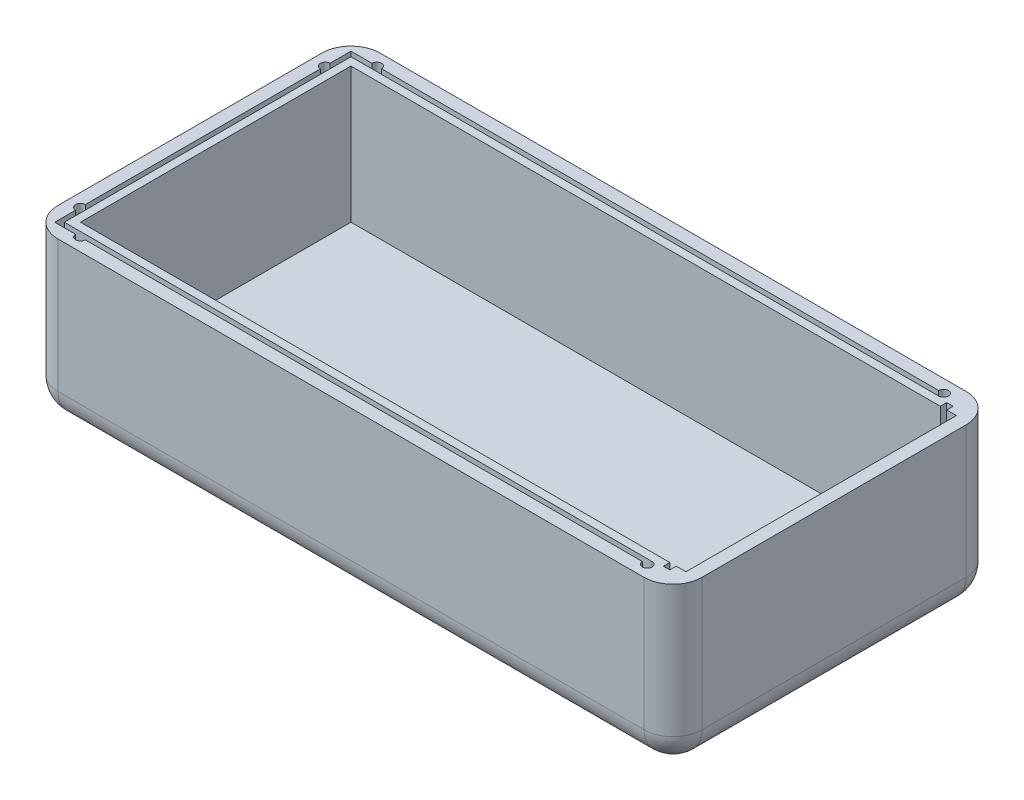
SolidWorks part; units mm, degrees
other "Исправление1"
sketch "Эскиз3"
other "Исправление2"
sketch "Эскиз4"
other "Исправление3"
sketch "Эскиз5" plane through (0, 25, 70) normal (-0.7989, 0.4591, 0.3886) x (0.5563, 0.3183, 0.7676)
other "Детальный элемент1"
other "Детальный элемент2"
other "Детальный элемент3"
ref_plane "Спереди" through (0, 0, 0) normal (0, 0, 1) x (1, 0, 0)
ref_plane "Сверху" through (0, 0, 0) normal (0, 1, 0) x (1, 0, 0)
ref_plane "Справа" through (0, 0, 0) normal (1, 0, 0) x (0, 0, -1)
sketch "Эскиз1" plane through (0, 0, 0) normal (0, 1, 0) x (1, 0, 0)
  line L1 (0, 0) -> (100, 0)
  line L2 (0, 0) -> (0, -50)
  line L3 (0, -50) -> (100, -50)
  line L4 (100, 0) -> (100, -50)
  dimension "D1" = 50
  dimension "D2" = 100
extrude "Бобышка-Вытянуть1" add sketch "Эскиз1" along normal blind 25
shell "Оболочка1" thickness 4 removed face at (50, 25, 25)
fillet "Скругление1" radius 4.5 8 edges at (50, 0, 50) (100, 0, 25) (50, 0, 0) (0, 0, 25) (100, 12.5, 0) (100, 12.5, 50) (0, 12.5, 0) (0, 12.5, 50)
sketch "Эскиз2" plane through (0, 25, 0) normal (0, 1, 0) x (1, 0, 0)
  line L0 (50, -4) -> (50, -46) construction
  line L1 (96, -4) -> (4, -4) construction
  line L2 (4, -46) -> (96, -46) construction
  line L3 (4, -25) -> (96, -25) construction
  line L4 (4, -4) -> (4, -46) construction
  line L5 (96, -46) -> (96, -4) construction
  line L6 (95.5, 0) -> (4.5, 0) construction
  line L7 (4, -4) -> (4, -46) construction
  line L8 (96, -4) -> (4, -4) construction
  line L9 (2.75, -6) -> (2.75, -2.75)
  line L10 (6, -2.75) -> (2.75, -2.75)
  line L11 (2, -5.25) -> (2, -2)
  line L12 (2, -2) -> (5.25, -2)
  line L13 (97.25, -6) -> (97.25, -2.75)
  line L14 (98, -5.25) -> (98, -2)
  line L15 (94, -2.75) -> (97.25, -2.75)
  line L16 (98, -2) -> (94.75, -2)
  line L17 (98, -48) -> (94.75, -48)
  line L18 (94, -47.25) -> (97.25, -47.25)
  line L19 (98, -44.75) -> (98, -48)
  line L20 (97.25, -44) -> (97.25, -47.25)
  line L21 (2, -48) -> (5.25, -48)
  line L22 (2, -44.75) -> (2, -48)
  line L23 (6, -47.25) -> (2.75, -47.25)
  line L24 (2.75, -44) -> (2.75, -47.25)
  line L25 (2, -6.75) -> (2, -43.25)
  line L26 (2.75, -44) -> (2.75, -6)
  line L27 (6, -2.75) -> (94, -2.75)
  line L28 (93.25, -2) -> (6.75, -2)
  line L29 (98, -6.75) -> (98, -43.25)
  line L30 (97.25, -6) -> (97.25, -44)
  line L31 (94, -47.25) -> (6, -47.25)
  line L32 (6.75, -48) -> (93.25, -48)
  line L33 (97.25, -47.25) -> (97.25, -48)
  line L34 (97.25, -2.75) -> (97.25, -2)
  circle A0 centre (6, -2) radius 0.75
  circle A1 centre (2, -6) radius 0.75
  circle A2 centre (98, -6) radius 0.75
  circle A3 centre (94, -2) radius 0.75
  circle A4 centre (94, -48) radius 0.75
  circle A5 centre (98, -44) radius 0.75
  circle A6 centre (2, -44) radius 0.75
  circle A7 centre (6, -48) radius 0.75
  dimension "D1" = 1.5
  dimension "D4" = 1.5
  dimension "D2" = 2
  dimension "D3" = 2
  dimension "D5" = 2
  dimension "D6" = 2
extrude "Вырез-Вытянуть1" cut sketch "Эскиз2" against normal blind 5 contours A0 | A1 L9 L10 A0 L12 L11 | A1 | A4 | A3 | A6 | L21 A7 L23 L24 A6 L22 | A7 region at (2.5703, 25, 5.4297) region at (2, 25, 6) region at (2, 25, 44) region at (2.6934, 25, 45.625) region at (6, 25, 2) region at (94, 25, 2) region at (6, 25, 48) region at (94, 25, 48)
extrude "Вырез-Вытянуть3" cut sketch "Эскиз2<6>" against normal blind 2.5 contours L25 A6 L26 A1 | L27 A3 L28 A0 | L31 A7 L32 A4 region at (2.3768, 25, 25) region at (50, 25, 2.3758) region at (50, 25, 47.6242)
sketch "Эскиз2<6>" plane through (0, 25, 0) normal (0, 1, 0) x (1, 0, 0) same geometry as "Эскиз2"
sketch "Эскиз7" plane through (0, 4, 0) normal (0, 1, 0) x (1, 0, 0)
  line L0 (96, -4) -> (4, -4) construction
  line L1 (95.5, -4) -> (96.5, -4)
  line L2 (95.5, -4) -> (95.5, -46)
  line L3 (95.5, -46) -> (96.5, -46)
  line L4 (96.5, -4) -> (96.5, -46)
  line L5 (4, -46) -> (96, -46) construction
  line L7 (100, -45.5) -> (100, -4.5) construction
  dimension "D1" = 1
  dimension "D2" = 3.5
sketch "Эскиз8" plane through (96, 0, 0) normal (-1, 0, 0) x (0, 0, 1)
  line L0 (4, 25) -> (4, 4) construction
  line L1 (7, 20.5) -> (43, 20.5)
  line L2 (7, 20.5) -> (7, 8.5)
  line L3 (7, 8.5) -> (43, 8.5)
  line L4 (43, 20.5) -> (43, 8.5)
  line L5 (46, 25) -> (46, 4) construction
  line L6 (46, 25) -> (4, 25) construction
  line L7 (46, 4) -> (4, 4) construction
  dimension "D1" = 3
  dimension "D2" = 3
  dimension "D3" = 4.5
  dimension "D4" = 4.5
extrude "Вырез-Вытянуть4" cut sketch "Эскиз8" against normal blind 3
sketch "Эскиз9" plane through (96, 0, 0) normal (-1, 0, 0) x (0, 0, 1)
  line L0 (4, 4) -> (4, 25)
  line L1 (4, 25) -> (46, 25)
  line L2 (46, 25) -> (46, 4)
  line L3 (46, 4) -> (4, 4)
extrude "Вырез-Вытянуть7" cut sketch "Эскиз9" against normal blind 2
extrude "Вырез-Вытянуть8" cut sketch "Эскиз7" against normal blind 1
sketch "Эскиз11" plane through (0, 0, 4) normal (0, 0, 1) x (1, 0, 0)
  line L0 (98, 25) -> (4, 25) construction
  line L1 (95.5, 4) -> (96.5, 4)
  line L2 (95.5, 4) -> (95.5, 25)
  line L3 (95.5, 25) -> (96.5, 25)
  line L4 (96.5, 4) -> (96.5, 25)
extrude "Вырез-Вытянуть10" cut sketch "Эскиз11" against normal blind 1
sketch "Эскиз12" plane through (0, 0, 46) normal (0, 0, -1) x (-1, 0, 0)
  line L0 (-4, 25) -> (-98, 25) construction
  line L1 (-96.5, 4) -> (-95.5, 4)
  line L2 (-96.5, 4) -> (-96.5, 25)
  line L3 (-96.5, 25) -> (-95.5, 25)
  line L4 (-95.5, 4) -> (-95.5, 25)
extrude "Вырез-Вытянуть11" cut sketch "Эскиз12" against normal blind 1
